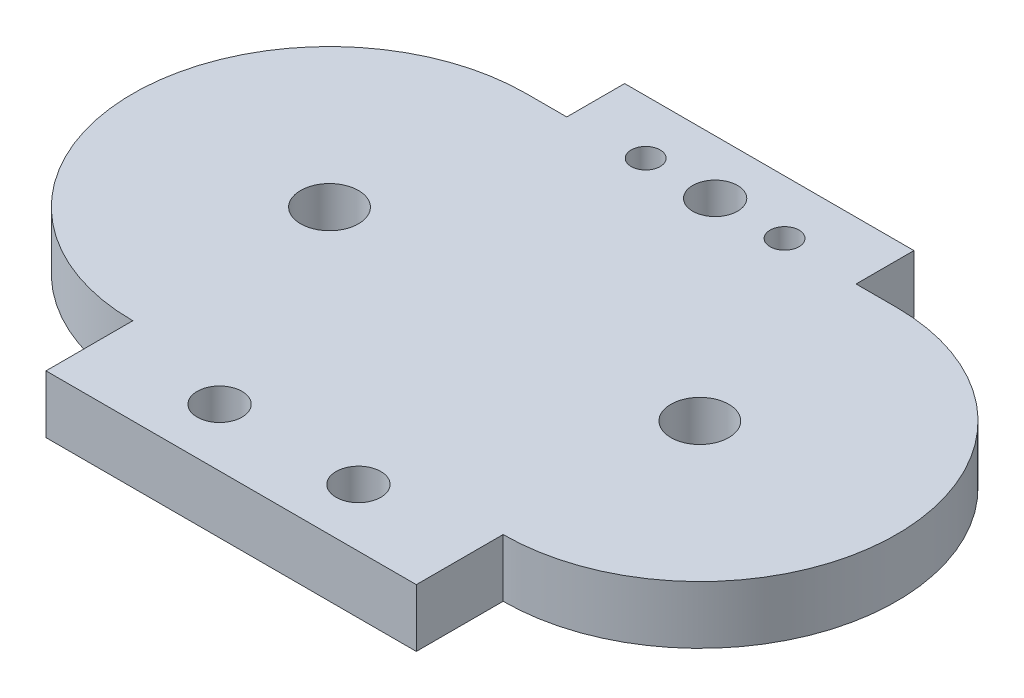
SolidWorks part; units mm, degrees
material "PLA"
ref_plane "Front Plane" through (0, 0, 0) normal (0, 0, 1) x (1, 0, 0)
ref_plane "Top Plane" through (0, 0, 0) normal (0, 1, 0) x (1, 0, 0)
ref_plane "Right Plane" through (0, 0, 0) normal (1, 0, 0) x (0, 0, -1)
sketch "Sketch1" plane through (0, 0, 0) normal (0, 1, 0) x (1, 0, 0)
  line L0 (-40.64, 0) -> (40.64, 0) construction
  line L1 (0, 34.29) -> (0, -31.75) construction
  line L2 (20.32, 0) -> (7.62, 21.997) construction
  line L3 (-20.32, 0) -> (-7.62, 21.997) construction
  line L11 (-20.32, 21.59) -> (-15.875, 21.59)
  line L13 (-15.875, 21.59) -> (-15.875, 27.94)
  line L14 (-15.875, 27.94) -> (15.875, 27.94)
  line L15 (15.875, 21.59) -> (15.875, 27.94)
  line L16 (20.32, 21.59) -> (15.875, 21.59)
  line L17 (-20.32, -21.59) -> (-20.32, -31.115)
  line L18 (-20.32, -31.115) -> (20.32, -31.115)
  line L19 (20.32, -31.115) -> (20.32, -21.59)
  circle A3 centre (20.32, 0) radius 3.175
  circle A4 centre (7.62, 21.997) radius 1.5875
  circle A5 centre (-20.32, 0) radius 3.175
  circle A6 centre (-7.62, 21.997) radius 1.5875
  arc A10 (-20.32, 21.59) -> (-20.32, -21.59) centre (-20.32, 0) ccw
  arc A11 (20.32, 21.59) -> (20.32, -21.59) centre (20.32, 0) cw
  point P21 (0, 27.94)
  dimension "D1" = 25.4
  dimension "D4" = 6.35
  dimension "D5" = 3.175
  dimension "D6" = 21.59
  dimension "D2" = 60
  dimension "D3" = 20.32
  dimension "D7" = 6.35
  dimension "D8" = 31.75
  dimension "D9" = 9.525
extrude "Boss-Extrude1" add sketch "Sketch1" along normal blind 6.35 contours A6 A3 A4 A5 region at (0, 0, 1.4901)
sketch "Sketch4" plane through (0, 6.35, 0) normal (0, 1, 0) x (1, 0, 0)
  line L1 (-20.32, -21.59) -> (-20.32, -31.115) construction
  line L2 (-20.32, -31.115) -> (20.32, -31.115) construction
  line L3 (20.32, -31.115) -> (20.32, -21.59) construction
  point P0 (-7.62, 21.997)
  point P1 (0, 21.997)
  point P2 (20.32, 0)
  point P4 (7.62, -24.765)
  point P8 (7.62, 21.997)
  point P9 (-20.32, 0)
  point P10 (-7.62, -24.765)
  dimension "D1" = 12.7
  dimension "D2" = 6.35
  dimension "D3" = 12.7
  dimension "D4" = 7.62
hole_wizard "#10 (0.1935) Diameter Hole1" positions "Sketch5" profile "Sketch6" hole size "#10" standard "ANSI Inch" end condition through all
sketch "Sketch5" plane through (0, 6.35, 0) normal (0, 1, 0) x (1, 0, 0)
  point P6 (0, 21.997)
  point P9 (0, 21.997)
  point P11 (-7.62, -24.765)
  point P14 (7.62, -24.765)
sketch "Sketch6" plane through (0, 6.35, -21.997) normal (1, 0, 0) x (0, 0, 1)
  line L0 (0, 0) -> (0, 6.35)
  line L1 (0, 6.35) -> (2.4574, 6.35)
  line L2 (2.4574, 6.35) -> (2.4574, 0)
  line L5 (2.4574, 0) -> (0, 0)
  line L11 (0, -6.35) -> (0, 107.95) construction
  dimension "Thru Hole Dia." = 4.9149
  dimension "Thru Hole Depth" = 6.35
shell "Shell2" [suppressed] thickness 2.54
sketch "Sketch3" [suppressed] plane through (0, 0, 0) normal (0, -1, 0) x (1, 0, 0)
  line L0 (-36.478, -40.64) -> (-27.7857, 8.89)
  line L1 (-27.7857, 8.89) -> (27.7857, 8.89)
  line L2 (27.7857, 8.89) -> (36.478, -40.64)
  line L3 (36.478, -40.64) -> (-36.478, -40.64)
  circle A0 centre (-20.32, 0) radius 8.89 construction
  circle A1 centre (20.32, 0) radius 8.89 construction
extrude "Cut-Extrude1" [suppressed] cut sketch "Sketch3" against normal up to surface (2.54 mm away)
